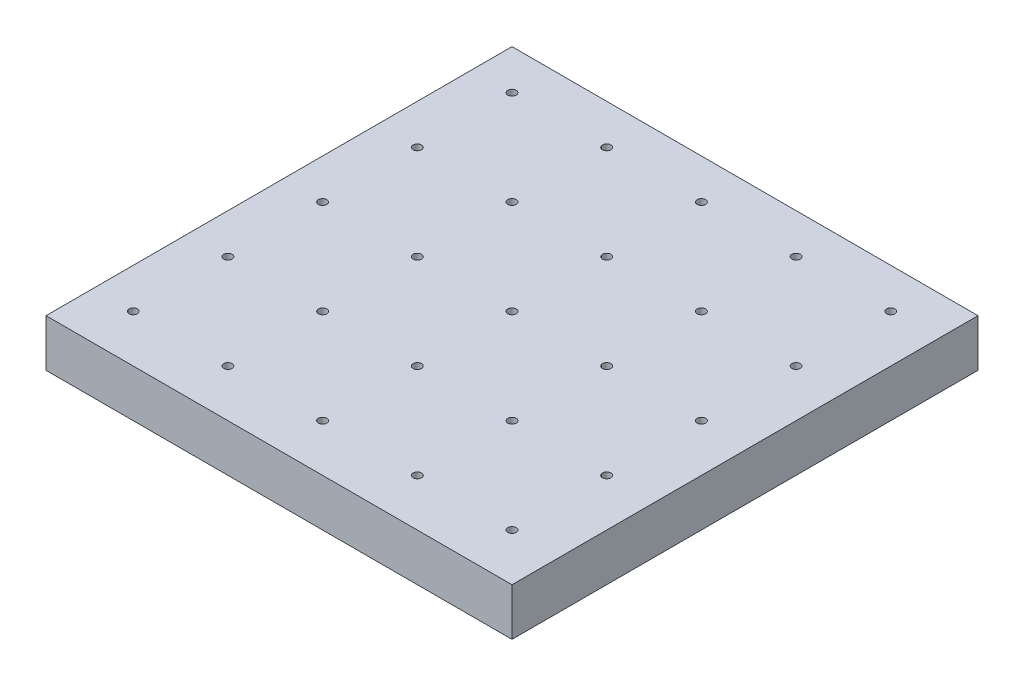
SolidWorks part; units mm, degrees
ref_plane "Front Plane" through (0, 0, 0) normal (0, 0, 1) x (1, 0, 0)
ref_plane "Top Plane" through (0, 0, 0) normal (0, 1, 0) x (1, 0, 0)
ref_plane "Right Plane" through (0, 0, 0) normal (1, 0, 0) x (0, 0, -1)
sketch "Sketch1" plane through (0, 0, 0) normal (0, 1, 0) x (1, 0, 0)
  line L1 (-62.5, 62.5) -> (62.5, 62.5)
  line L2 (-62.5, 62.5) -> (-62.5, -62.5)
  line L3 (-62.5, -62.5) -> (62.5, -62.5)
  line L4 (62.5, 62.5) -> (62.5, -62.5)
  line L5 (-62.5, 62.5) -> (62.5, -62.5) construction
  line L6 (-62.5, -62.5) -> (62.5, 62.5) construction
  point P0 (0, 0)
  dimension "D1" = 125
extrude "Boss-Extrude1" add sketch "Sketch1" along normal blind 12.7
hole_wizard "#4-40 Tapped Hole1" positions "3DSketch1" profile "Sketch2" tap size "#4-40" standard "ANSI Inch" end condition through all
sketch3d "3DSketch1"
  line L0 (-62.5, 12.7, 62.5) -> (62.5, 12.7, 62.5) construction
  line L1 (62.5, 12.7, 62.5) -> (62.5, 12.7, -62.5) construction
  point P0 (49.8, 12.7, 49.8)
  dimension "D2" = 12.7
  dimension "D1" = 12.7
cosmetic thread "Hole Thread1"
sketch "Sketch2" plane through (49.8, 12.7, 49.8) normal (1, 0, 0) x (0, 0, 1)
  line L0 (0, 0) -> (0, 12.7)
  line L1 (0, 12.7) -> (1.1303, 12.7)
  line L2 (1.1303, 12.7) -> (1.1303, 0)
  line L5 (1.1303, 0) -> (0, 0)
  line L11 (0, -6.35) -> (0, 107.95) construction
  dimension "Thru Tap Drill Dia." = 2.2606
  dimension "Thru Tap Drill Depth" = 12.7
pattern_linear "LPattern1" count 5 spacing 25.4 along (-1, 0, 0) count 5 spacing 25.4 along (0, 0, -1) of "#4-40 Tapped Hole1"
cosmetic thread "Hole Thread2"
cosmetic thread "Hole Thread3"
cosmetic thread "Hole Thread4"
cosmetic thread "Hole Thread5"
cosmetic thread "Hole Thread6"
cosmetic thread "Hole Thread7"
cosmetic thread "Hole Thread8"
cosmetic thread "Hole Thread9"
cosmetic thread "Hole Thread10"
cosmetic thread "Hole Thread11"
cosmetic thread "Hole Thread12"
cosmetic thread "Hole Thread13"
cosmetic thread "Hole Thread14"
cosmetic thread "Hole Thread15"
cosmetic thread "Hole Thread16"
cosmetic thread "Hole Thread17"
cosmetic thread "Hole Thread18"
cosmetic thread "Hole Thread19"
cosmetic thread "Hole Thread20"
cosmetic thread "Hole Thread21"
cosmetic thread "Hole Thread22"
cosmetic thread "Hole Thread23"
cosmetic thread "Hole Thread24"
cosmetic thread "Hole Thread25"
cosmetic thread "Hole Thread26"
cosmetic thread "Hole Thread27"
cosmetic thread "Hole Thread28"
cosmetic thread "Hole Thread29"
cosmetic thread "Hole Thread30"
cosmetic thread "Hole Thread31"
cosmetic thread "Hole Thread32"
cosmetic thread "Hole Thread33"
cosmetic thread "Hole Thread34"
cosmetic thread "Hole Thread35"
cosmetic thread "Hole Thread36"
equation "\"D2@3DSketch1\"=\"D1@3DSketch1\""
